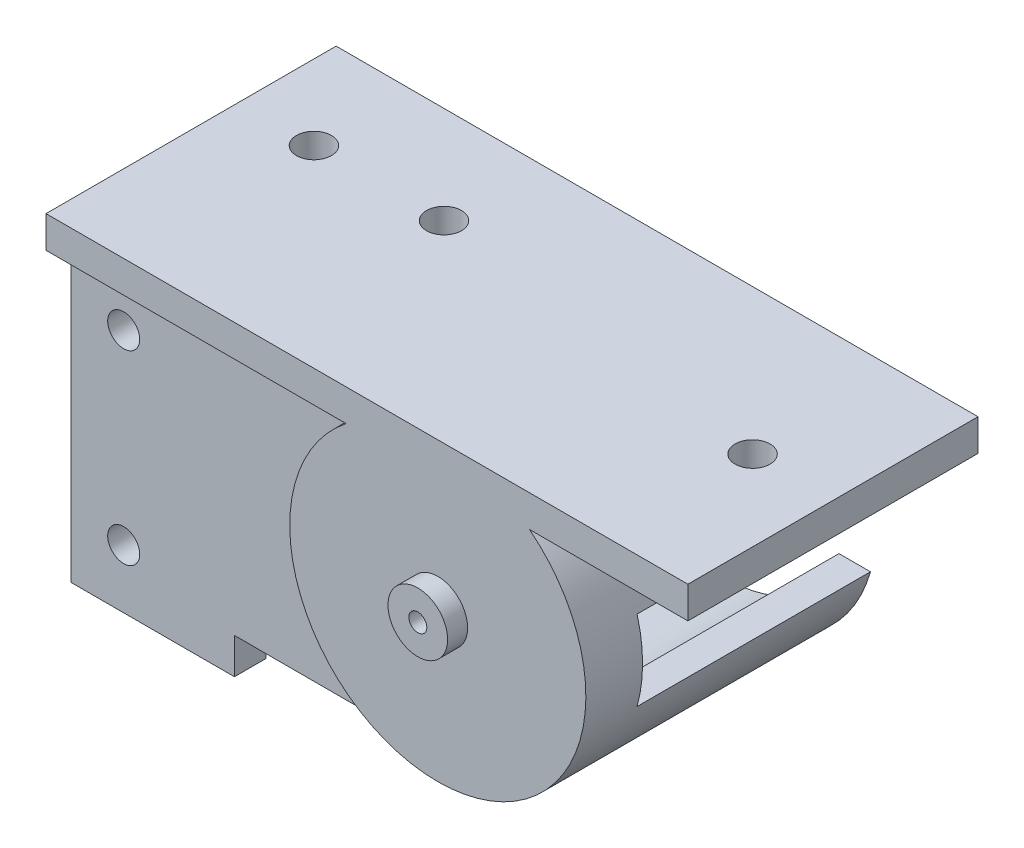
SolidWorks part; units mm, degrees
ref_plane "Front Plane" through (0, 0, 0) normal (0, 0, 1) x (1, 0, 0)
ref_plane "Top Plane" through (0, 0, 0) normal (0, 1, 0) x (1, 0, 0)
ref_plane "Right Plane" through (0, 0, 0) normal (1, 0, 0) x (0, 0, -1)
sketch "Sketch1" plane through (0, 0, 0) normal (0, 0, 1) x (1, 0, 0)
  circle A2 centre (0, 0) radius 11.8
  circle A3 centre (0, 0) radius 14.8
  dimension "D1" = 23.6
  dimension "D2" = 3
extrude "Boss-Extrude2" add sketch "Sketch1" along normal blind 23.33
sketch "Sketch2" plane through (0, 0, 23.33) normal (0, 0, 1) x (1, 0, 0)
  circle A0 centre (0, 0) radius 9.25
  circle A2 centre (0, 0) radius 14.8
  circle A3 centre (0, 0) radius 14.8
  dimension "D1" = 18.5
  dimension "D2" = 0
extrude "Boss-Extrude3" add sketch "Sketch2" along normal blind 3.34
sketch "Sketch3" plane through (0, 0, 26.67) normal (0, 0, 1) x (1, 0, 0)
  circle A0 centre (0, 0) radius 2.98
  circle A2 centre (0, 0) radius 14.8
  circle A3 centre (0, 0) radius 14.8
  dimension "D2" = 5.96
  dimension "D1" = 0
extrude "Boss-Extrude4" add sketch "Sketch3" along normal blind 2.33
sketch "Sketch4" plane through (0, 0, 29) normal (0, 0, 1) x (1, 0, 0)
  circle A0 centre (0, 0) radius 0.9
  circle A1 centre (0, 0) radius 2.98
extrude "Boss-Extrude5" add sketch "Sketch4" along normal blind 2 separate body
sketch "Sketch8" plane through (0, 0, 0) normal (0, 0, 1) x (1, 0, 0)
  line L0 (-39.166, 14.8) -> (25, 14.8)
  line L1 (-39.166, 14.8) -> (-39.166, 11.62)
  line L3 (25, 11.62) -> (25, 14.8)
  line L4 (-39.166, 11.62) -> (-9.166, 11.62)
  line L5 (9.166, 11.62) -> (25, 11.62)
  circle A3 centre (0, 0) radius 14.8 construction
  circle A4 centre (0, 0) radius 14.8
  point P3 (0, 14.8)
  point P4 (0, 14.8)
  dimension "D1" = 3.18
  dimension "D2" = 30
extrude "Boss-Extrude8" add sketch "Sketch8" along normal up to surface (29 mm away) contours A4 L0 L1 L4 | A4 L5 L3 L0 region at (-22.6413, 13.2681, 0) region at (15.5059, 13.312, 0) up to face at (14.8, 0, 29)
sketch "Sketch10" plane through (0, 11.62, 0) normal (0, -1, 0) x (1, 0, 0)
  line L0 (-39.166, 29) -> (-39.166, 0) construction
  line L1 (-39.166, 26.5) -> (-22.8307, 26.5)
  line L2 (-39.166, 26.5) -> (-39.166, 23.32)
  line L3 (-39.166, 23.32) -> (-22.8307, 23.32)
  line L4 (-22.8307, 26.5) -> (-22.8307, 23.32)
  line L5 (-39.166, 29) -> (-9.166, 29) construction
  dimension "D1" = 3.18
  dimension "D2" = 2.5
extrude "Boss-Extrude10" add sketch "Sketch10" along normal blind 30
sketch "Sketch12" plane through (0, 0, 26.5) normal (0, 0, 1) x (1, 0, 0)
  line L0 (0, -14.8) -> (-22.8307, -14.8)
  line L4 (-22.8307, 11.62) -> (-39.166, 11.62)
  line L5 (9.166, 11.62) -> (25, 11.62)
  line L6 (25, 11.62) -> (25, 14.8)
  line L7 (25, 14.8) -> (-39.166, 14.8)
  line L8 (-39.166, 14.8) -> (-39.166, 11.62)
  line L9 (-39.166, 11.62) -> (-9.166, 11.62)
  line L10 (9.166, 11.62) -> (25, 11.62)
  line L11 (25, 11.62) -> (25, 14.8)
  line L12 (25, 14.8) -> (-39.166, 14.8)
  line L13 (-39.166, 14.8) -> (-39.166, 11.62)
  line L14 (-39.166, 11.62) -> (-9.166, 11.62)
  line L15 (-39.166, 11.62) -> (-39.166, -18.38)
  line L16 (-39.166, -18.38) -> (-22.8307, -18.38)
  line L17 (-22.8307, -18.38) -> (-22.8307, 11.62)
  line L18 (-22.8307, 11.62) -> (-39.166, 11.62)
  line L19 (-39.166, 11.62) -> (-39.166, -18.38)
  line L20 (-39.166, -18.38) -> (-22.8307, -18.38)
  line L21 (-22.8307, -18.38) -> (-22.8307, 11.62)
  arc A1 (-9.166, 11.62) -> (9.166, 11.62) centre (0, 0) ccw
  arc A2 (-9.166, 11.62) -> (9.166, 11.62) centre (0, 0) ccw
  line M14 (-22.8307, -18.38) -> (-22.8307, 11.62)
  dimension "D1" = 0
  dimension "D2" = 0
extrude "Boss-Extrude11" add sketch "Sketch12" against normal up to surface (3.18 mm away) contours A2 L14 L0 M14 region at (-17.1816, -2.5174, 26.5) up to face at (-30.9983, -3.38, 23.32)
sketch "Sketch11" plane through (0, 0, 26.5) normal (0, 0, 1) x (1, 0, 0)
  line L0 (-35.5, 7.1857) -> (-35.5, 6.0857) construction
  line L1 (-32.3, 7.1857) -> (-32.3, 6.0857) construction
  line L2 (-22.8307, -18.38) -> (-22.8307, -14.8) construction
  line L3 (-35.5, -12.5143) -> (-35.5, -13.6143) construction
  line L4 (-32.3, -12.5143) -> (-32.3, -13.6143) construction
  line L5 (-39.166, -18.38) -> (-22.8307, -18.38) construction
  arc A0 (-32.3, 7.1857) -> (-35.5, 7.1857) centre (-33.9, 7.1857) ccw construction
  arc A1 (-35.5, 6.0857) -> (-32.3, 6.0857) centre (-33.9, 6.0857) ccw construction
  arc A2 (-32.3, -12.5143) -> (-35.5, -12.5143) centre (-33.9, -12.5143) ccw construction
  arc A3 (-35.5, -13.6143) -> (-32.3, -13.6143) centre (-33.9, -13.6143) ccw construction
  circle A4 centre (-33.9, 6.0857) radius 1.6
  circle A5 centre (-33.9, -12.5143) radius 1.6
  dimension "D1" = 9.4693
  dimension "D2" = 1.6
  dimension "D3" = 1.6
  dimension "D5" = 1.1
  dimension "D6" = 18.6
  dimension "D4" = 1.1
  dimension "D7" = 5.8657
extrude "Cut-Extrude1" cut sketch "Sketch11" against normal through all
sketch "Sketch13" plane through (0, 0, 0) normal (0, 0, -1) x (-1, 0, 0)
  line L0 (-14.2492, 4) -> (14.2492, 4)
  line L1 (-14.2492, -4) -> (14.2492, -4)
  line L2 (-14.8, 0) -> (14.8, 0) construction
  line L3 (0, 0) -> (0, 4) construction
  line L4 (0, -4) -> (0, 0) construction
  line L5 (9.166, 11.62) -> (39.166, 11.62)
  line L6 (39.166, 11.62) -> (39.166, 14.8)
  line L7 (39.166, 14.8) -> (-25, 14.8)
  line L8 (-25, 14.8) -> (-25, 11.62)
  line L9 (-25, 11.62) -> (-9.166, 11.62)
  line L10 (9.166, 11.62) -> (39.166, 11.62)
  line L11 (39.166, 11.62) -> (39.166, 14.8)
  line L12 (39.166, 14.8) -> (-25, 14.8)
  line L13 (-25, 14.8) -> (-25, 11.62)
  line L14 (-25, 11.62) -> (-9.166, 11.62)
  circle A0 centre (0, 0) radius 11.8 construction
  circle A1 centre (0, 0) radius 11.8
  arc A2 (-9.166, 11.62) -> (9.166, 11.62) centre (0, 0) ccw
  arc A4 (-9.166, 11.62) -> (9.166, 11.62) centre (0, 0) ccw
  arc M13 (-9.166, 11.62) -> (9.166, 11.62) centre (0, 0) ccw
  circle M20 centre (0, 0) radius 11.8
  dimension "D2" = 8
  dimension "D1" = 0
extrude "Cut-Extrude3" cut sketch "Sketch13" against normal up to surface (23.33 mm away) contours L1 L0 M13 M20 | L1 L0 M20 M13 region at (13.0912, 0, 0) region at (-13.0912, 0, 0) up to face at (9.25, 0, 23.33)
fillet "Fillet2" radius 2 1 edges at (-24.166, 11.62, 23.32)
sketch "Sketch14" plane through (0, 14.8, 0) normal (0, 1, 0) x (1, 0, 0)
  line L0 (0, -27.5) -> (0, -32) construction
  line L8 (-9.166, -21.32) -> (-9.166, 0) construction
  line L10 (-39.166, 0) -> (-39.166, -21.32) construction
  line L11 (-9.166, 0) -> (-39.166, 0) construction
  line L16 (9.166, -29) -> (22.7188, -29) construction
  line L17 (9.166, 0) -> (9.166, -29) construction
  line L18 (22.7188, 0) -> (9.166, 0) construction
  line L19 (22.7188, -29) -> (22.7188, 0) construction
  line L26 (0, -35.18) -> (0, -32) construction
  line L29 (-39.166, -21.32) -> (-9.166, -21.32) construction
  line L34 (6.2362, -26.5) -> (6.2362, -8) construction
  line L35 (6.2362, -8) -> (-6.2362, -8) construction
  line L36 (-6.2362, -8) -> (-6.2362, -26.5) construction
  line L37 (-4.5979, -27.5) -> (4.5979, -27.5) construction
  line L38 (0, -35.18) -> (0, -69.3642) construction
  line L39 (-31.666, -9.7142) -> (-39.166, -9.7142) construction
  line L40 (-20.5, -31.84) -> (20.5, -31.84)
  line L41 (-20.5, -31.84) -> (-20.5, -35.34)
  line L42 (-20.5, -35.34) -> (20.5, -35.34)
  line L43 (20.5, -31.84) -> (20.5, -35.34)
  line L88 (-58.986, -69.3642) -> (-23.991, -69.3642) construction
  line L89 (-23.991, -69.3642) -> (-23.991, -66.1842) construction
  line L90 (-23.991, -66.1842) -> (-15.766, -66.1842) construction
  line L91 (-15.766, -66.1842) -> (-15.766, -58.3842) construction
  line L92 (-15.766, -58.3842) -> (-17.516, -58.3842) construction
  line L93 (-17.516, -58.3842) -> (-17.516, -56.0042) construction
  line L94 (-17.516, -56.0042) -> (-15.766, -56.0042) construction
  line L95 (-15.766, -56.0042) -> (-15.766, -50.3842) construction
  line L96 (-15.766, -50.3842) -> (-12.916, -50.3842) construction
  line L97 (-12.916, -50.3842) -> (-12.916, -56.0042) construction
  line L98 (-12.916, -56.0042) -> (-11.166, -56.0042) construction
  line L99 (-11.166, -56.0042) -> (-11.166, -58.3842) construction
  line L100 (-11.166, -58.3842) -> (-12.916, -58.3842) construction
  line L101 (-12.916, -58.3842) -> (-12.916, -66.1842) construction
  line L102 (-12.916, -66.1842) -> (-4.691, -66.1842) construction
  line L103 (-4.691, -66.1842) -> (-4.691, -69.3642) construction
  line L104 (-4.691, -69.3642) -> (30.304, -69.3642) construction
  line L105 (30.304, -69.3642) -> (30.304, -29.0142) construction
  line L106 (30.304, -29.0142) -> (33.484, -29.0142) construction
  line L107 (33.484, -29.0142) -> (33.484, -9.7142) construction
  line L108 (33.484, -9.7142) -> (30.304, -9.7142) construction
  line L109 (30.304, -9.7142) -> (30.304, 30.6358) construction
  line L110 (30.304, 30.6358) -> (-4.691, 30.6358) construction
  line L111 (-4.691, 30.6358) -> (-4.691, 27.4558) construction
  line L112 (-4.691, 27.4558) -> (-12.916, 27.4558) construction
  line L113 (-12.916, 27.4558) -> (-12.916, 19.6558) construction
  line L114 (-12.916, 19.6558) -> (-11.166, 19.6558) construction
  line L115 (-11.166, 19.6558) -> (-11.166, 17.2758) construction
  line L116 (-11.166, 17.2758) -> (-12.916, 17.2758) construction
  line L117 (-12.916, 17.2758) -> (-12.916, 11.6558) construction
  line L118 (-12.916, 11.6558) -> (-15.766, 11.6558) construction
  line L119 (-15.766, 11.6558) -> (-15.766, 17.2758) construction
  line L120 (-15.766, 17.2758) -> (-17.516, 17.2758) construction
  line L121 (-17.516, 17.2758) -> (-17.516, 19.6558) construction
  line L122 (-17.516, 19.6558) -> (-15.766, 19.6558) construction
  line L123 (-15.766, 19.6558) -> (-15.766, 27.4558) construction
  line L124 (-15.766, 27.4558) -> (-23.991, 27.4558) construction
  line L125 (-23.991, 27.4558) -> (-23.991, 30.6358) construction
  line L126 (-23.991, 30.6358) -> (-58.986, 30.6358) construction
  line L127 (-58.986, 30.6358) -> (-58.986, -9.7142) construction
  line L128 (-58.986, -9.7142) -> (-62.166, -9.7142) construction
  line L129 (-62.166, -9.7142) -> (-62.166, -29.0142) construction
  line L130 (-62.166, -29.0142) -> (-58.986, -29.0142) construction
  line L131 (-58.986, -29.0142) -> (-58.986, -69.3642) construction
  line L132 (-20.5, -31.84) -> (20.5, -35.34) construction
  line L133 (-20.5, -35.34) -> (20.5, -31.84) construction
  line L134 (-31.666, -9.7142) -> (-31.666, -21.32) construction
  line L135 (16.9651, -14.5) -> (22.7188, -14.5) construction
  line L136 (16.9651, -14.5) -> (16.9651, 0) construction
  line L137 (-31.666, -9.7142) -> (-18.666, -9.7142) construction
  circle A0 centre (-31.666, -9.7142) radius 1.75
  circle A1 centre (16.9651, -14.5) radius 1.75
  circle A2 centre (-18.666, -9.7142) radius 1.75
  spline S4 degree 3 poles (-6.2362, -26.5) (-6.2362, -26.6789) (-6.1611, -26.8491) (-5.9318, -27.1198) (-5.7828, -27.2213) (-5.4648, -27.3723) (-5.2931, -27.4227) (-4.9491, -27.4862) (-4.7745, -27.5) (-4.5979, -27.5) knots 0 0 0 0 0.25 0.25 0.5 0.5 0.75 0.75 1 1 1 1 construction
  spline S5 degree 3 poles (4.5979, -27.5) (4.7746, -27.5) (4.9496, -27.4862) (5.2953, -27.4222) (5.4661, -27.3718) (5.7829, -27.2211) (5.9319, -27.1198) (6.1615, -26.8485) (6.2362, -26.6789) (6.2362, -26.5) knots 0 0 0 0 0.25 0.25 0.5 0.5 0.75 0.75 1 1 1 1 construction
  point P14 (0, -33.59)
  point P46 (-39.166, 0)
  dimension "D6" = 3.5
  dimension "D4" = 41
  dimension "D5" = 3.5
  dimension "D7" = 7.5
  dimension "D9" = 13
extrude "Cut-Extrude4" cut sketch "Sketch14" against normal through all contours A0 | A2 | A1 region at (-31.666, 14.8, 9.7142) region at (16.9651, 14.8, 14.5) region at (-18.666, 14.8, 9.7142)
sketch "Sketch15" plane through (0, 0, 26.5) normal (0, 0, 1) x (1, 0, 0)
  line L0 (0, 0) -> (0, -14.8) construction
  line L1 (0, -14.8) -> (0, -18.8) construction
  line L2 (6, -18.8) -> (6, -13.5292)
  line L3 (-6, -18.8) -> (-6, -13.5292)
  line L7 (9.166, 11.62) -> (25, 11.62)
  line L8 (25, 11.62) -> (25, 14.8)
  line L9 (25, 14.8) -> (-39.166, 14.8)
  line L10 (-39.166, 14.8) -> (-39.166, 11.62)
  line L11 (-39.166, 11.62) -> (-9.166, 11.62)
  line L12 (9.166, 11.62) -> (25, 11.62)
  line L13 (25, 11.62) -> (25, 14.8)
  line L14 (25, 14.8) -> (-39.166, 14.8)
  line L15 (-39.166, 14.8) -> (-39.166, 11.62)
  line L16 (-39.166, 11.62) -> (-9.166, 11.62)
  circle A0 centre (0, -18.8) radius 4
  arc A1 (-9.166, 11.62) -> (9.166, 11.62) centre (0, 0) ccw construction
  circle A2 centre (0, -18.8) radius 6
  arc A4 (-9.166, 11.62) -> (9.166, 11.62) centre (0, 0) ccw
  arc A5 (-9.166, 11.62) -> (9.166, 11.62) centre (0, 0) ccw
  dimension "D1" = 8
  dimension "D2" = 12
  dimension "D3" = 0
